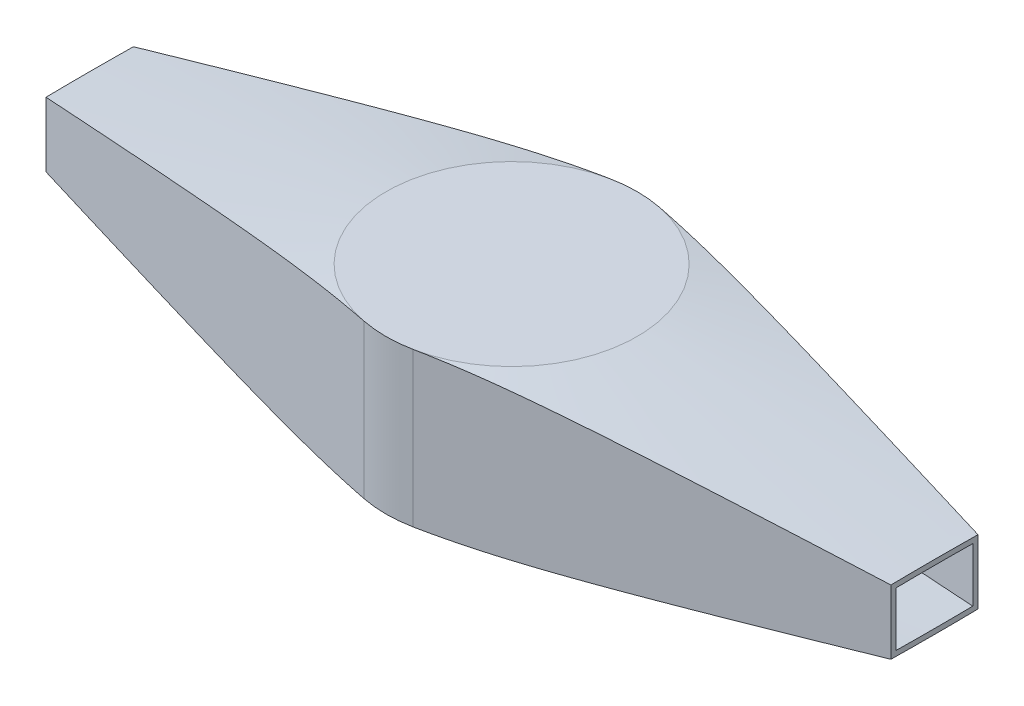
SolidWorks part; units mm, degrees
note: The reader was unsure of these and kept them because the rebuilt part matched: shared geometry of "草图16<5>".
other "相机2"
other "相机3"
material "PEN"
ref_plane "前视基准面" through (0, 0, 0) normal (0, 0, 1) x (1, 0, 0)
ref_plane "上视基准面" through (0, 0, 0) normal (0, 1, 0) x (1, 0, 0)
ref_plane "右视基准面" through (0, 0, 0) normal (1, 0, 0) x (0, 0, -1)
sketch "草图1" plane through (0, 0, 0) normal (0, 1, 0) x (1, 0, 0)
  circle A0 centre (0, 0) radius 49
extrude "凸台-拉伸1" add sketch "草图1" along normal mid plane 60
sketch "草图2" plane through (0, 0, 0) normal (0, 1, 0) x (1, 0, 0)
  line L8 (0, 0) -> (165, 0)
  line L9 (0, 0) -> (-164.6213, 0)
  line L11 (165, 0) -> (165, 16.9895)
  line L16 (165, 0) -> (165, -16.9895)
  line L17 (-164.6213, 0) -> (-164.6213, 17.0652)
  line L18 (-164.6213, 0) -> (-164.6213, -17.0652)
  line L21 (-250, 0) -> (-9.604, 48.0496)
  line L22 (-250, 0) -> (-9.604, -48.0496)
  line L23 (250, 0) -> (9.604, -48.0496)
  line L24 (250, 0) -> (9.604, 48.0496)
  circle A2 centre (0, 0) radius 49 construction
  arc A3 (-9.604, 48.0496) -> (9.604, 48.0496) centre (0, 0) cw
  arc A4 (-9.604, -48.0496) -> (9.604, -48.0496) centre (0, 0) ccw
sketch "草图14" plane through (0, 0, 0) normal (0, 1, 0) x (1, 0, 0)
  line L5 (-250, 0) -> (-9.604, -48.0496)
  line L6 (250, 0) -> (9.604, -48.0496) construction
  line L7 (9.604, -48.0496) -> (250, 0)
  line L8 (250, 0) -> (9.604, 48.0496)
  line L9 (-9.604, 48.0496) -> (-250, 0)
  arc A2 (-9.604, -48.0496) -> (9.604, -48.0496) centre (0, 0) ccw
  arc A3 (9.604, 48.0496) -> (-9.604, 48.0496) centre (0, 0) ccw
  arc A4 (9.604, 48.0496) -> (-9.604, 48.0496) centre (0, 0) ccw construction
sketch "草图15" plane through (0, 0, 0) normal (0, 1, 0) x (1, 0, 0)
  line L6 (-9.604, -48.0496) -> (-164.6213, -17.0652)
  line L7 (-164.6213, -17.0652) -> (-164.6213, 17.0652)
  line L8 (-164.6213, 17.0652) -> (-9.604, 48.0496)
  line L9 (9.604, 48.0496) -> (165, 16.9895)
  line L10 (165, 16.9895) -> (165, -16.9895)
  line L11 (165, -16.9895) -> (9.604, -48.0496)
  line L12 (250, 0) -> (9.604, -48.0496) construction
  circle A0 centre (0, 0) radius 49 construction
  arc A2 (-9.604, 48.0496) -> (9.604, 48.0496) centre (0, 0) cw
  arc A3 (9.604, 48.0496) -> (-9.604, 48.0496) centre (0, 0) ccw construction
  arc A4 (9.604, -48.0496) -> (-9.604, -48.0496) centre (0, 0) cw
  arc A5 (-9.604, -48.0496) -> (9.604, -48.0496) centre (0, 0) ccw construction
sketch "草图16" plane through (0, 0, 0) normal (0, 1, 0) x (1, 0, 0)
  circle A0 centre (0, 0) radius 250
loft "放样1" add profiles "草图16" section "草图16" section edge at (0, 30, 49)
loft "放样3" add profiles "草图16<5>" section "草图16<5>" section edge at (0, -30, 49)
sketch "草图16<5>" plane through (0, 0, 0) normal (0, 1, 0) x (1, 0, 0) same geometry as "草图16"
extrude "切除-拉伸1" cut sketch "草图14" against normal through all both and the other way through all flip side to cut
shell "抽壳1" thickness 2
extrude "切除-拉伸2" cut sketch "草图15" against normal through all both and the other way through all flip side to cut
